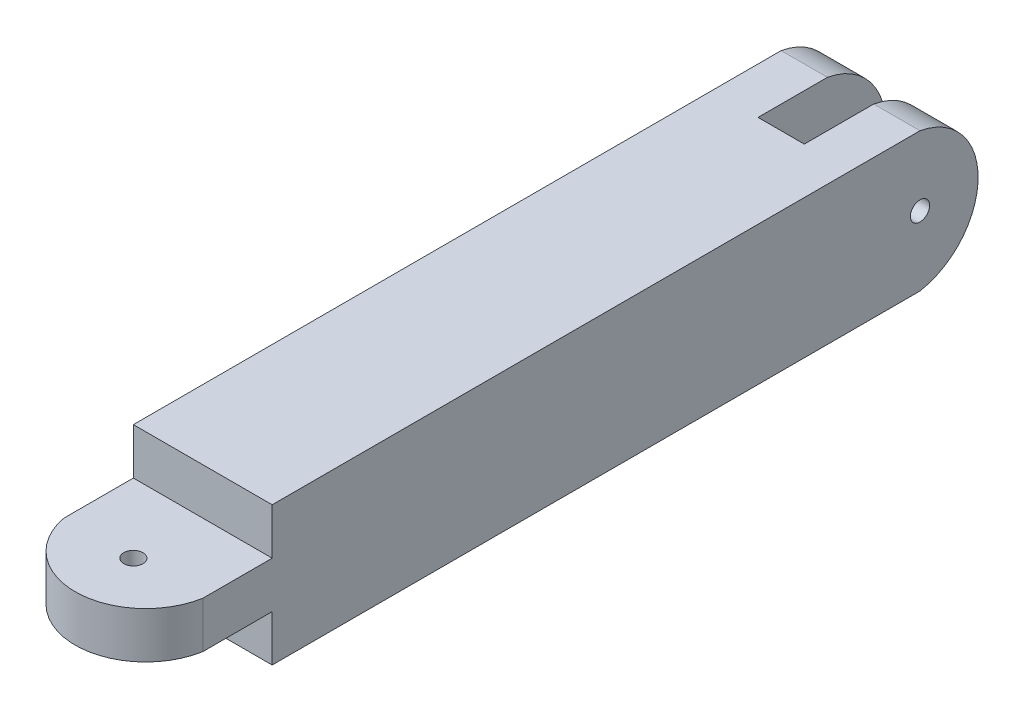
SolidWorks part; units mm, degrees
ref_plane "Front Plane" through (0, 0, 0) normal (0, 0, 1) x (1, 0, 0)
ref_plane "Top Plane" through (0, 0, 0) normal (0, 1, 0) x (1, 0, 0)
ref_plane "Right Plane" through (0, 0, 0) normal (1, 0, 0) x (0, 0, -1)
sketch "Sketch2" plane through (0, 0, 0) normal (0, 0, 1) x (1, 0, 0)
  line L1 (-30, 30) -> (30, 30)
  line L2 (-30, 30) -> (-30, -30)
  line L3 (-30, -30) -> (30, -30)
  line L4 (30, 30) -> (30, -30)
  line L5 (-30, 30) -> (30, -30) construction
  line L6 (-30, -30) -> (30, 30) construction
  point P0 (0, 0)
  dimension "D1" = 60
  dimension "D2" = 60
extrude "Boss-Extrude1" add sketch "Sketch2" along normal blind 250
ref_plane "Plane1" through (0, 0, 0) normal (0, 0, -1) x (-1, 0, 0)
sketch "Sketch3" plane through (0, 0, 0) normal (0, 0, -1) x (-1, 0, 0)
  line L0 (-30, 30) -> (30, 30) construction
  line L1 (30, -30) -> (10, -30)
  line L2 (30, -30) -> (30, 30)
  line L3 (30, 30) -> (10, 30)
  line L4 (10, -30) -> (10, 30)
  line L5 (30, -30) -> (-30, -30) construction
  line L6 (-30, 30) -> (-10, 30)
  line L7 (-30, 30) -> (-30, -30)
  line L8 (-30, -30) -> (-10, -30)
  line L9 (-10, 30) -> (-10, -30)
  dimension "D1" = 20
  dimension "D2" = 20
extrude "Boss-Extrude2" add sketch "Sketch3" along normal blind 30
ref_plane "Plane2" through (30, 0, 0) normal (1, 0, 0) x (0, 0, -1)
sketch "Sketch4" plane through (30, 0, 0) normal (1, 0, 0) x (0, 0, -1)
  line L0 (30, 30) -> (30, -30)
  arc A0 (30, 30) -> (30, -30) centre (24.6689, 0) cw
  dimension "D1" = 30.47
extrude "Boss-Extrude3" add sketch "Sketch4" against normal blind 20
ref_plane "Plane3" through (-30, 0, 0) normal (-1, 0, 0) x (0, 0, 1)
sketch "Sketch5" plane through (-30, 0, 0) normal (-1, 0, 0) x (0, 0, 1)
  line L0 (-30, -30) -> (-30, 30)
  arc A0 (-30, -30) -> (-30, 30) centre (-24.6689, 0) cw
  dimension "D1" = 30.47
extrude "Boss-Extrude4" add sketch "Sketch5" against normal blind 20
ref_plane "Plane4" through (0, 0, 250) normal (0, 0, 1) x (1, 0, 0)
sketch "Sketch6" plane through (0, 0, 250) normal (0, 0, 1) x (1, 0, 0)
  line L0 (30, -30) -> (30, 30) construction
  line L1 (-30, 10) -> (30, 10)
  line L2 (-30, 10) -> (-30, -10)
  line L3 (-30, -10) -> (30, -10)
  line L4 (30, 10) -> (30, -10)
  line L5 (-30, 10) -> (30, -10) construction
  line L6 (-30, -10) -> (30, 10) construction
  point P0 (0, 0)
  dimension "D1" = 20
extrude "Boss-Extrude5" add sketch "Sketch6" along normal blind 30
ref_plane "Plane5" through (0, 10, 0) normal (0, 1, 0) x (1, 0, 0)
sketch "Sketch7" plane through (0, 10, 0) normal (0, 1, 0) x (1, 0, 0)
  line L0 (30, -280) -> (-30, -280)
  arc A0 (30, -280) -> (-30, -280) centre (0, -274.6689) cw
  dimension "D1" = 30.47
extrude "Boss-Extrude6" add sketch "Sketch7" against normal blind 20
ref_plane "Plane6" through (0, 0, 250) normal (0, 0, 1) x (1, 0, 0)
sketch "Sketch8" plane through (0, 0, 250) normal (0, 0, 1) x (1, 0, 0)
  line L1 (-25.25, -25.25) -> (25.25, -25.25)
  line L2 (-25.25, -25.25) -> (-25.25, 25.25)
  line L3 (-25.25, 25.25) -> (25.25, 25.25)
  line L4 (25.25, -25.25) -> (25.25, 25.25)
  line L5 (-25.25, -25.25) -> (25.25, 25.25) construction
  line L6 (-25.25, 25.25) -> (25.25, -25.25) construction
  point P0 (0, 0)
  dimension "D1" = 50.5
  dimension "D2" = 50.5
extrude "Cut-Extrude2" cut sketch "Sketch8" against normal blind 130 and the other way blind 5 from offset 10 contours L3 L4 L1 L2 offset against normal yes
ref_plane "Plane7" through (0, -10, 0) normal (0, -1, 0) x (-1, 0, 0)
sketch "Sketch9" plane through (0, -10, 0) normal (0, -1, 0) x (-1, 0, 0)
  line L0 (30, -250) -> (-30, -250) construction
  circle A0 centre (0, -280) radius 4.15
  dimension "D1" = 8.3
  dimension "D2" = 30
extrude "Cut-Extrude3" cut sketch "Sketch9" against normal blind 130
ref_plane "Plane8" through (30, 0, 0) normal (1, 0, 0) x (0, 0, -1)
ref_plane "Plane9" through (10, 0, 0) normal (-1, 0, 0) x (0, 0, 1)
sketch "Sketch11" plane through (10, 0, 0) normal (-1, 0, 0) x (0, 0, 1)
  line L0 (0, -30) -> (0, 30) construction
  circle A0 centre (-30, 0) radius 4.15
  dimension "D2" = 8.3
  dimension "D1" = 30
extrude "Cut-Extrude4" cut sketch "Sketch11" against normal through all
ref_plane "Plane10" through (-10, 0, 0) normal (1, 0, 0) x (0, 0, -1)
sketch "Sketch12" plane through (-10, 0, 0) normal (1, 0, 0) x (0, 0, -1)
  line L0 (0, 30) -> (0, -30) construction
  circle A0 centre (30, 0) radius 4.15
  dimension "D1" = 30
  dimension "D2" = 8.3
extrude "Cut-Extrude5" cut sketch "Sketch12" against normal through all
